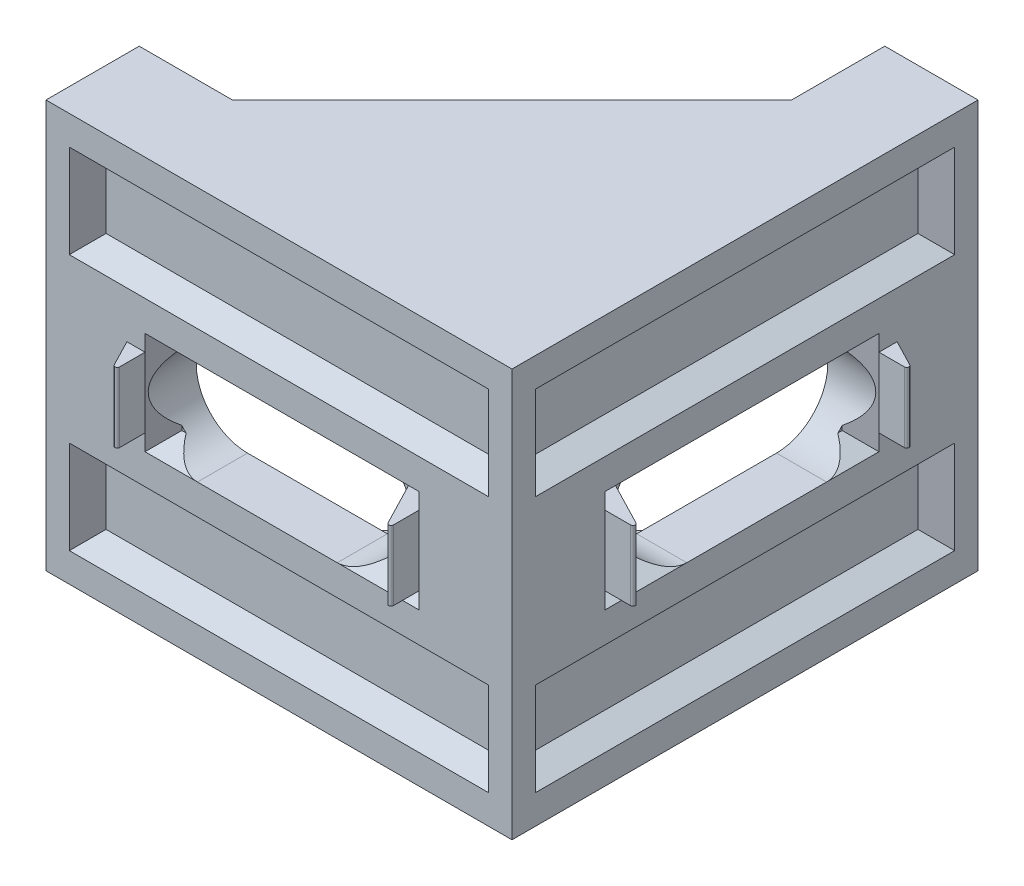
SolidWorks part; units mm, degrees
material "1060 合金"
ref_plane "前视基准面" through (0, 0, 0) normal (0, 0, 1) x (1, 0, 0)
ref_plane "上视基准面" through (0, 0, 0) normal (0, 1, 0) x (1, 0, 0)
ref_plane "右视基准面" through (0, 0, 0) normal (1, 0, 0) x (0, 0, -1)
sketch "草图1" plane through (0, 0, 0) normal (0, 1, 0) x (1, 0, 0)
  line L0 (0, 0) -> (0, 40)
  line L1 (0, 0) -> (-40, 0)
  line L2 (-40, 0) -> (-40, 8)
  line L3 (-40, 8) -> (-32, 8)
  line L4 (-32, 8) -> (-8, 32)
  line L5 (-8, 32) -> (-8, 40)
  line L6 (-8, 40) -> (0, 40)
  dimension "D1" = 40
  dimension "D2" = 40
  dimension "D3" = 8
  dimension "D4" = 8
  dimension "D5" = 8
  dimension "D6" = 8
extrude "凸台-拉伸1" add sketch "草图1" along normal blind 3
sketch "草图2" plane through (0, 0, 0) normal (1, 0, 0) x (0, 0, -1)
  line L0 (27, 13.1) -> (15, 13.1)
  line L1 (40, 3) -> (0, 3)
  line L2 (40, 3) -> (40, 32)
  line L3 (40, 32) -> (0, 32)
  line L4 (0, 3) -> (0, 32)
  line L5 (27, 21.9) -> (15, 21.9)
  line L6 (32, 0) -> (8, 0) construction
  arc A0 (27, 13.1) -> (27, 21.9) centre (27, 17.5) ccw
  arc A1 (15, 21.9) -> (15, 13.1) centre (15, 17.5) ccw
  dimension "D6" = 8.8
  dimension "D1" = 40
  dimension "D2" = 29
  dimension "D3" = 17.5
  dimension "D4" = 15
  dimension "D5" = 12
extrude "凸台-拉伸2" add sketch "草图2" against normal blind 4.3
sketch "草图3" plane through (0, 32, 0) normal (0, 1, 0) x (1, 0, 0)
  line L0 (-4.3, 40) -> (0, 40)
  line L1 (0, 40) -> (0, 0)
  line L2 (0, 0) -> (-4.3, 0)
  line L7 (-40, 0) -> (-4.3, 0)
  line L8 (-4.3, 0) -> (-4.3, 40)
  line L9 (-4.3, 40) -> (-8, 40)
  line L10 (-8, 40) -> (-8, 32)
  line L11 (-8, 32) -> (-32, 8)
  line L12 (-32, 8) -> (-40, 8)
  line L13 (-40, 8) -> (-40, 0)
  line L14 (-40, 0) -> (-4.3, 0)
  line L16 (-4.3, 40) -> (-8, 40)
  line L17 (-8, 40) -> (-8, 32)
  line L18 (-8, 32) -> (-32, 8)
  line L19 (-32, 8) -> (-40, 8)
  line L20 (-40, 8) -> (-40, 0)
  dimension "D1" = 0
extrude "凸台-拉伸3" add sketch "草图3" along normal blind 3
sketch "草图4" plane through (0, 0, 0) normal (0, 0, 1) x (1, 0, 0)
  line L0 (-27, 17.5) -> (-15, 17.5) construction
  line L1 (-4.3, 3) -> (-40, 3)
  line L2 (-4.3, 3) -> (-4.3, 32)
  line L3 (-4.3, 32) -> (-40, 32)
  line L4 (-40, 3) -> (-40, 32)
  line L5 (-27, 21.9) -> (-15, 21.9)
  line L6 (-27, 13.1) -> (-15, 13.1)
  line L7 (0, 35) -> (0, 0) construction
  line L8 (-40, 0) -> (0, 0) construction
  arc A0 (-15, 13.1) -> (-15, 21.9) centre (-15, 17.5) ccw
  arc A1 (-27, 21.9) -> (-27, 13.1) centre (-27, 17.5) ccw
  dimension "D1" = 8.8
  dimension "D2" = 15
  dimension "D3" = 12
  dimension "D4" = 17.5
extrude "凸台-拉伸4" add sketch "草图4" against normal blind 4.3
sketch "草图5" plane through (0, 0, 0) normal (1, 0, 0) x (0, 0, -1)
  line L0 (0, 35) -> (40, 35) construction
  line L1 (38, 32.5) -> (2, 32.5)
  line L2 (38, 32.5) -> (38, 24.5)
  line L3 (38, 24.5) -> (2, 24.5)
  line L4 (2, 32.5) -> (2, 24.5)
  line L5 (38, 10.5) -> (2, 10.5)
  line L6 (38, 10.5) -> (38, 2.5)
  line L7 (38, 2.5) -> (2, 2.5)
  line L8 (2, 10.5) -> (2, 2.5)
  line L9 (0, 0) -> (40, 0) construction
  line L10 (0, 35) -> (0, 0) construction
  line L11 (40, 35) -> (40, 0) construction
  line L12 (27, 21.9) -> (15, 21.9) construction
  line L13 (31.5, 21.9) -> (8, 21.9)
  line L14 (31.5, 21.9) -> (31.5, 13.1)
  line L15 (31.5, 13.1) -> (8, 13.1)
  line L16 (8, 21.9) -> (8, 13.1)
  line L17 (15, 13.1) -> (27, 13.1) construction
  point P20 (34.7579, 23.0274)
  dimension "D1" = 2.5
  dimension "D2" = 2.5
  dimension "D3" = 2
  dimension "D4" = 2
  dimension "D5" = 2
  dimension "D6" = 2
  dimension "D7" = 8
  dimension "D8" = 8
  dimension "D9" = 8.5
  dimension "D10" = 8
extrude "切除-拉伸1" cut sketch "草图5" against normal blind 2 draft 30
sketch "草图6" plane through (0, 0, 0) normal (0, 0, 1) x (1, 0, 0)
  line L0 (-15, 21.9) -> (-27, 21.9) construction
  line L1 (-38, 2.5) -> (-2, 2.5)
  line L2 (-38, 2.5) -> (-38, 10.5)
  line L3 (-38, 10.5) -> (-2, 10.5)
  line L4 (-2, 2.5) -> (-2, 10.5)
  line L5 (-38, 24.5) -> (-2, 24.5)
  line L6 (-38, 24.5) -> (-38, 32.5)
  line L7 (-38, 32.5) -> (-2, 32.5)
  line L8 (-2, 24.5) -> (-2, 32.5)
  line L9 (-31.5, 13.1) -> (-8, 13.1)
  line L10 (-31.5, 13.1) -> (-31.5, 21.9)
  line L11 (-31.5, 21.9) -> (-8, 21.9)
  line L12 (-8, 13.1) -> (-8, 21.9)
  line L13 (-27, 13.1) -> (-15, 13.1) construction
  line L14 (-40, 35) -> (-40, 0) construction
  line L15 (0, 35) -> (0, 0) construction
  line L16 (-40, 35) -> (0, 35) construction
  line L17 (-40, 0) -> (0, 0) construction
  dimension "D1" = 8.5
  dimension "D2" = 8
  dimension "D3" = 2
  dimension "D4" = 8
  dimension "D5" = 2.5
  dimension "D6" = 2
  dimension "D7" = 2.5
  dimension "D8" = 8
extrude "切除-拉伸2" cut sketch "草图6" against normal blind 2 draft 30
ref_plane "基准面1" through (0, 17.5, 0) normal (0, 1, 0) x (1, 0, 0)
sketch "草图7" plane through (0, 17.5, 0) normal (0, 1, 0) x (1, 0, 0)
  line L0 (-2, 9.1547) -> (-2, 8)
  line L1 (-2, 8) -> (3, 8)
  line L3 (3, 8) -> (-2, 10.5918)
  line L4 (-2, 29.9712) -> (-2, 31.5)
  line L11 (-2, 31.5) -> (3, 31.5)
  line L12 (0, 8) -> (0, 15)
  line L13 (-2, 9.1547) -> (0, 8)
  line L14 (-2, 12.0288) -> (-2, 9.1547)
  line L15 (0, 8) -> (0, 15) construction
  line L16 (-2, 9.1547) -> (0, 8) construction
  line L18 (-2, 30.3453) -> (-2, 29.9712)
  line L19 (0, 31.5) -> (-2, 30.3453)
  line L20 (0, 27) -> (0, 31.5)
  line L21 (-2, 30.3453) -> (-2, 29.9712) construction
  line L22 (0, 31.5) -> (-2, 30.3453) construction
  line L23 (0, 27) -> (0, 31.5) construction
  line L24 (3, 31.5) -> (-2, 34.0918)
  line L25 (-2, 34.0918) -> (-2, 31.5)
  line L26 (-2, 8) -> (-2, 10.5918)
  line L27 (-2, 10.5918) -> (-2, 12.0288)
  ellipse E2 centre (-7.621, 15) end of major axis (0, 15) minor radius 4.4 (-2, 12.0288) -> (0, 15) ccw
  ellipse E3 centre (-7.621, 15) end of major axis (0, 15) minor radius 4.4 (-2, 12.0288) -> (0, 15) ccw construction
  ellipse E4 centre (-7.621, 27) end of major axis (-15.242, 27) minor radius 4.4 (0, 27) -> (-2, 29.9712) ccw
  ellipse E5 centre (-7.621, 27) end of major axis (-15.242, 27) minor radius 4.4 (0, 27) -> (-2, 29.9712) ccw construction
  dimension "D3" = 3
  dimension "D1" = 2.5918
  dimension "D5" = 3
  dimension "D2" = 0
  dimension "D4" = 0
extrude "凸台-拉伸5" add sketch "草图7" along normal mid plane 6 contours L26 L0 L1 L3 | L24 L25 L11 region at (-1.3333, 17.5, -8.3849) region at (-0.9869, 17.5, -9.3182) region at (1, 17.5, -8.5184) region at (-0.3333, 17.5, -32.3639)
sketch "草图8" plane through (0, 17.5, 0) normal (0, 1, 0) x (1, 0, 0)
  line L0 (-8, -3) -> (-8, 2)
  line L1 (-8, 2) -> (-10.5918, 2)
  line L2 (-10.5918, 2) -> (-8, -3)
  line L3 (-9.1547, 2) -> (-12.0288, 2)
  line L4 (-8, 0) -> (-9.1547, 2)
  line L5 (-15, 0) -> (-8, 0)
  line L7 (-8, 0) -> (-9.1547, 2)
  line L8 (-15, 0) -> (-8, 0)
  line L9 (-31.5, 2) -> (-31.5, -3)
  line L10 (-31.5, -3) -> (-34.0918, 2)
  line L11 (-34.0918, 2) -> (-31.5, 2)
  line L12 (-31.5, 0) -> (-27, 0)
  line L13 (-30.3453, 2) -> (-31.5, 0)
  line L14 (-29.9712, 2) -> (-30.3453, 2)
  line L15 (-31.5, 0) -> (-27, 0)
  line L16 (-30.3453, 2) -> (-31.5, 0)
  line L17 (-29.9712, 2) -> (-30.3453, 2)
  ellipse E1 centre (-15, 7.621) end of major axis (-15, 0) minor radius 4.4 (-15, 0) -> (-12.0288, 2) ccw
  ellipse E2 centre (-15, 7.621) end of major axis (-15, 0) minor radius 4.4 (-15, 0) -> (-12.0288, 2) ccw
  ellipse E3 centre (-27, 7.621) end of major axis (-27, 0) minor radius 4.4 (-29.9712, 2) -> (-27, 0) ccw
  ellipse E4 centre (-27, 7.621) end of major axis (-27, 0) minor radius 4.4 (-29.9712, 2) -> (-27, 0) ccw
  dimension "D2" = 3
  dimension "D4" = 2.5918
  dimension "D5" = 3
  dimension "D1" = 0
  dimension "D3" = 0
extrude "凸台-拉伸6" add sketch "草图8" along normal mid plane 6 contours L8 L2 L0 | L11 L10 L9 | L2 L8 L7 L1 region at (-8.5184, 17.5, 1) region at (-9.3182, 17.5, -0.9869) region at (-32.3639, 17.5, -0.3333)
fillet "圆角2" radius 0.2 4 edges at (3, 17.5, -31.5) (3, 17.5, -8) (-31.5, 17.5, 3) (-8, 17.5, 3)
